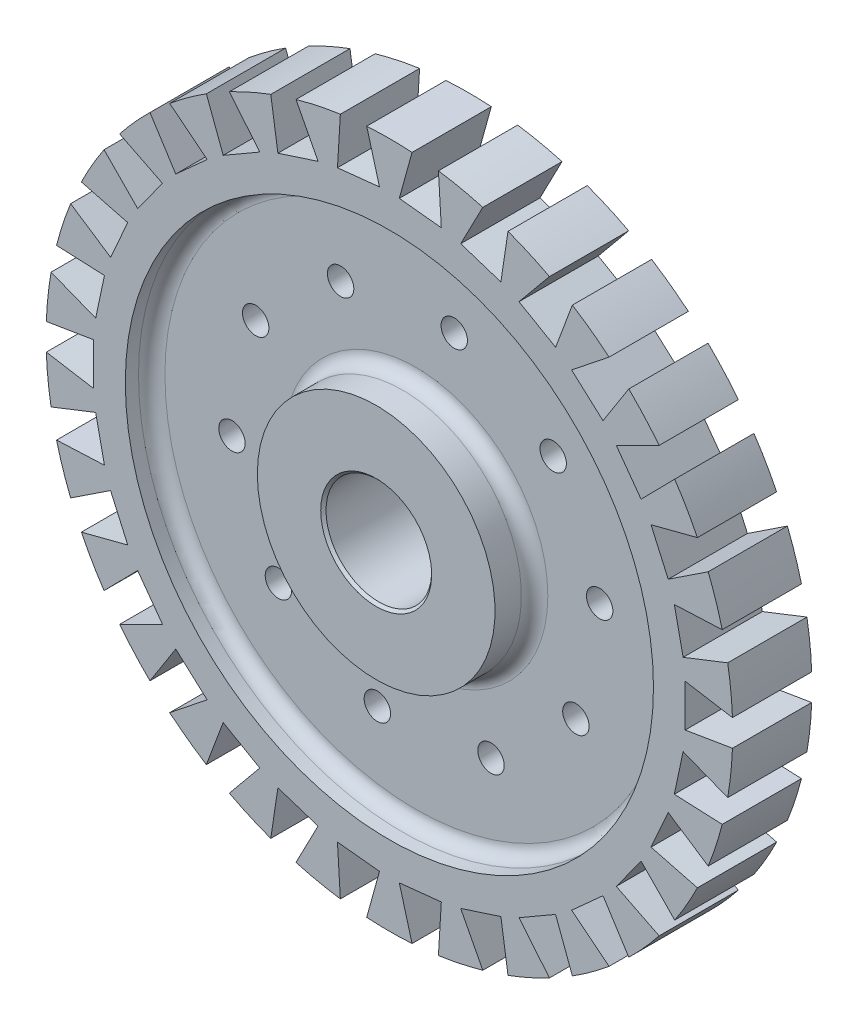
SolidWorks part; units mm, degrees
ref_plane "前视基准面" through (0, 0, 0) normal (0, 0, 1) x (1, 0, 0)
ref_plane "上视基准面" through (0, 0, 0) normal (0, 1, 0) x (1, 0, 0)
ref_plane "右视基准面" through (0, 0, 0) normal (1, 0, 0) x (0, 0, -1)
sketch "草图1" plane through (0, 0, 0) normal (0, 1, 0) x (1, 0, 0)
  line L0 (0, 0) -> (0, -1) construction
  line L1 (20, 0) -> (45, 0)
  line L2 (45, 0) -> (45, -15)
  line L3 (45, -15) -> (100, -15)
  line L4 (100, -15) -> (100, -5)
  line L5 (100, -5) -> (130, -5)
  line L6 (130, -5) -> (130, -35)
  line L7 (130, -35) -> (100, -35)
  line L8 (100, -35) -> (100, -25)
  line L9 (100, -25) -> (45, -25)
  line L10 (45, -25) -> (45, -40)
  line L11 (45, -40) -> (20, -40)
  line L12 (20, -40) -> (20, 0)
revolve "旋转1" add sketch "草图1" angle 360 about L0
fillet "圆角1" radius 5 4 edges at (-100, 0, 15) (-100, 0, 25) (-45, 0, 25) (-45, 0, 15)
chamfer "倒角1" distance 1 angle 45 2 edges at (-20, 0, 0) (-20, 0, 40)
ref_plane "基准面1" through (0, 0, 25) normal (0, 0, 1) x (1, 0, 0)
ref_plane "基准面2" through (0, 0, 40) normal (0, 0, 1) x (1, 0, 0)
sketch "草图3" plane through (0, 0, 40) normal (0, 0, 1) x (1, 0, 0)
  line L0 (112, 8) -> (135, 4.1667)
  line L1 (135, 4.1667) -> (135, -4.1667)
  line L2 (135, -4.1667) -> (112, -8)
  line L3 (112, -8) -> (112, 8)
extrude "切除-拉伸2" cut sketch "草图3" against normal through all
ref_axis "基准轴1" through (0, 0, 42) along (0, 0, -1)
pattern_circular "阵列(圆周)1" count 30 over 360 about axis through (0, 0, 42) along (0, 0, -1) of "切除-拉伸2"
sketch "草图4" plane through (0, 0, 40) normal (0, 0, 1) x (1, 0, 0)
  circle A0 centre (69.6165, 7.317) radius 5
  circle A1 centre (52.0201, 46.8391) radius 5
  circle A2 centre (14.5538, 68.4703) radius 5
  circle A3 centre (-28.4716, 63.9482) radius 5
  circle A4 centre (-60.6218, 35) radius 5
  circle A5 centre (-69.6165, -7.317) radius 5
  circle A6 centre (-52.0201, -46.8391) radius 5
  circle A7 centre (-14.5538, -68.4703) radius 5
  circle A8 centre (28.4716, -63.9482) radius 5
  circle A9 centre (60.6218, -35) radius 5
extrude "切除-拉伸3" cut sketch "草图4" against normal through all
